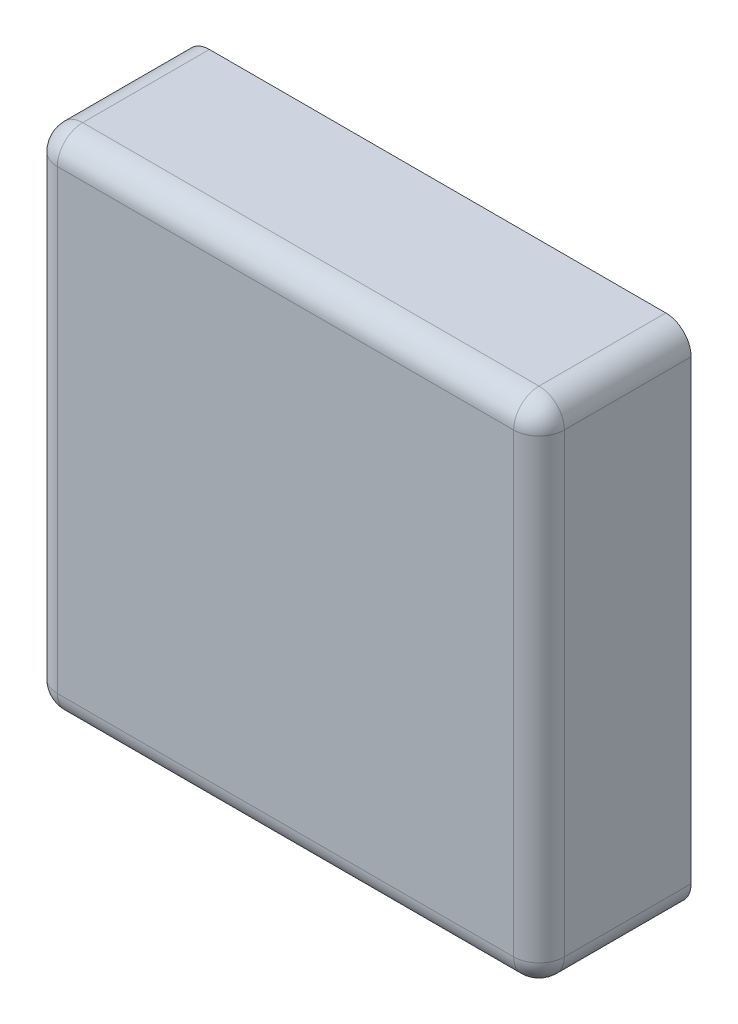
SolidWorks part; units mm, degrees
material "Silicon Dioxide"
ref_plane "Front Plane" through (0, 0, 0) normal (0, 0, 1) x (1, 0, 0)
ref_plane "Top Plane" through (0, 0, 0) normal (0, 1, 0) x (1, 0, 0)
ref_plane "Right Plane" through (0, 0, 0) normal (1, 0, 0) x (0, 0, -1)
sketch "Sketch1" plane through (0, 0, 0) normal (0, 0, 1) x (1, 0, 0)
  line L1 (-75.6362, 48.0134) -> (24.3638, 48.0134)
  line L2 (-75.6362, 48.0134) -> (-75.6362, -51.9866)
  line L3 (-75.6362, -51.9866) -> (24.3638, -51.9866)
  line L4 (24.3638, 48.0134) -> (24.3638, -51.9866)
  dimension "D1" = 100
  dimension "D2" = 100
extrude "Boss-Extrude1" add sketch "Sketch1" along normal blind 30
fillet "Fillet1" radius 5 8 edges at (-75.6362, -51.9866, 15) (24.3638, -51.9866, 15) (-25.6362, -51.9866, 30) (24.3638, -1.9866, 30) (24.3638, 48.0134, 15) (-75.6362, -1.9866, 30) (-75.6362, 48.0134, 15) (-25.6362, 48.0134, 30)
